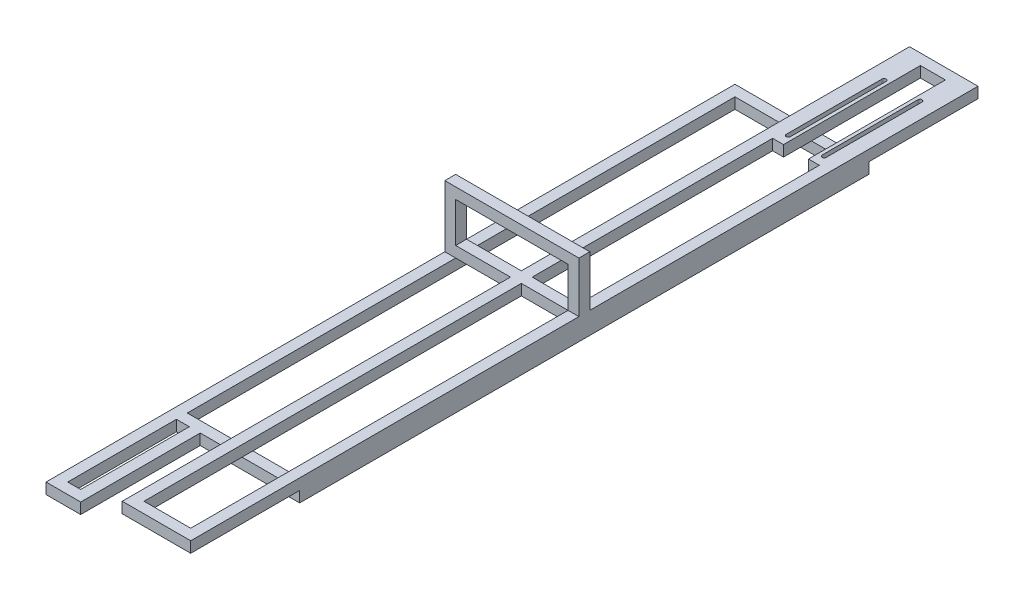
SolidWorks part; units mm, degrees
ref_plane "Front Plane" through (0, 0, 0) normal (0, 0, 1) x (1, 0, 0)
ref_plane "Top Plane" through (0, 0, 0) normal (0, 1, 0) x (1, 0, 0)
ref_plane "Right Plane" through (0, 0, 0) normal (1, 0, 0) x (0, 0, -1)
sketch "Sketch1" plane through (0, 0, 0) normal (0, 1, 0) x (1, 0, 0)
  line L1 (-50, 575) -> (50, 575)
  line L2 (-50, 575) -> (-50, -575)
  line L3 (-50, -575) -> (50, -575)
  line L4 (50, 575) -> (50, -575)
  line L8 (-34.125, 559.125) -> (34.125, 559.125)
  line L9 (34.125, 559.125) -> (34.125, -559.125)
  line L10 (-34.125, -559.125) -> (34.125, -559.125)
  line L11 (-34.125, 559.125) -> (-34.125, -559.125)
  point P4 (0, 575)
  point P6 (50, 0)
  dimension "D1" = 100
  dimension "D2" = 1150
  dimension "D3" = 15.875
extrude "Boss-Extrude1" add sketch "Sketch1" along normal blind 15.875
sketch "Sketch3" plane through (0, 15.875, 0) normal (0, 1, 0) x (1, 0, 0)
  line L0 (-145.875, 558.625) -> (-145.875, -591.375) construction
  line L2 (34.125, -223.912) -> (34.125, 400)
  line L3 (34.125, 400) -> (-130, 400)
  line L4 (-130, 220.5939) -> (-130, 400)
  line L6 (50, 415.875) -> (-145.875, 415.875)
  line L7 (-145.875, 217.7568) -> (-145.875, 415.875)
  line L9 (50, -312.7388) -> (50, 415.875)
  line L10 (-8.7312, 0) -> (8.7312, 0) construction
  line L11 (50, -312.7388) -> (50, -415.875)
  line L13 (-145.875, 217.7568) -> (-145.875, -415.875)
  line L14 (50, -415.875) -> (-145.875, -415.875)
  line L15 (-130, 220.5939) -> (-130, -400)
  line L16 (34.125, -223.912) -> (34.125, -400)
  line L18 (34.125, -400) -> (-130, -400)
  line L19 (50, -575) -> (50, 575) construction
  line L20 (50, -312.7388) -> (-145.875, 217.7568) construction
  line L21 (34.125, -223.912) -> (-130, 220.5939) construction
  point P0 (50, -312.7388)
  point P6 (-145.875, 415.875)
  point P12 (34.125, 0)
  point P22 (50, 0)
  dimension "D1" = 400
  dimension "D3" = 15.875
extrude "Boss-Extrude2" add sketch "Sketch3" against normal blind 15.875 from surface starting at face at (0, 0, 0)
sketch "Sketch5" plane through (0, 0, 0) normal (0, 0, 1) x (1, 0, 0)
  line L0 (-145.875, 959.91) -> (-145.875, -15.875) construction
  line L1 (50, 0) -> (-145.875, 0)
  line L2 (50, 0) -> (50, 90)
  line L3 (50, 90) -> (-145.875, 90)
  line L4 (-145.875, 0) -> (-145.875, 90)
  line L5 (34.125, 74.125) -> (-130, 74.125)
  line L6 (-130, 15.875) -> (-130, 74.125)
  line L7 (34.125, 15.875) -> (-130, 15.875)
  line L8 (34.125, 15.875) -> (34.125, 74.125)
  dimension "D1" = 90
  dimension "D2" = 15.875
extrude "Boss-Extrude3" add sketch "Sketch5" along normal mid plane 15.875
sketch "Sketch6" plane through (0, 0, 0) normal (0, -1, 0) x (1, 0, 0)
  line L6 (-34.125, -559.125) -> (-18.25, -559.125)
  line L7 (-34.125, -559.125) -> (-34.125, -359.125)
  line L8 (-34.125, -359.125) -> (-18.25, -359.125)
  line L9 (-18.25, -559.125) -> (-18.25, -359.125)
  line L10 (34.125, -559.125) -> (18.25, -559.125)
  line L11 (34.125, -559.125) -> (34.125, -359.125)
  line L12 (34.125, -359.125) -> (18.25, -359.125)
  line L13 (18.25, -559.125) -> (18.25, -359.125)
  line L14 (34.125, -559.125) -> (-34.125, -559.125) construction
  dimension "D1" = 15.875
  dimension "D2" = 15.875
  dimension "D4" = 200
extrude "Boss-Extrude4" add sketch "Sketch6" against normal blind 15.875
sketch "Sketch7" plane through (0, 0, 0) normal (0, -1, 0) x (1, 0, 0)
  line L0 (-26.1875, -374.125) -> (-26.1875, -514.125) construction
  line L1 (-23.1875, -374.125) -> (-23.1875, -514.125)
  line L2 (-29.1875, -374.125) -> (-29.1875, -514.125)
  line L3 (26.1875, -374.125) -> (26.1875, -514.125) construction
  line L4 (29.1875, -374.125) -> (29.1875, -514.125)
  line L5 (23.1875, -374.125) -> (23.1875, -514.125)
  line L6 (-18.25, -359.125) -> (-34.125, -359.125) construction
  line L7 (34.125, -359.125) -> (18.25, -359.125) construction
  arc A0 (-23.1875, -374.125) -> (-29.1875, -374.125) centre (-26.1875, -374.125) ccw
  arc A1 (-29.1875, -514.125) -> (-23.1875, -514.125) centre (-26.1875, -514.125) ccw
  arc A2 (29.1875, -374.125) -> (23.1875, -374.125) centre (26.1875, -374.125) ccw
  arc A3 (23.1875, -514.125) -> (29.1875, -514.125) centre (26.1875, -514.125) ccw
  point P2 (-26.1875, -444.125)
  point P7 (26.1875, -444.125)
  point P17 (-26.1875, -359.125)
  point P20 (26.1875, -359.125)
  dimension "D1" = 3
  dimension "D2" = 140
  dimension "D3" = 15
extrude "Cut-Extrude1" cut sketch "Sketch7" against normal blind 15.875
sketch "Sketch8" plane through (0, 0, 0) normal (0, 1, 0) x (1, 0, 0)
  line L1 (-95.25, -590.5) -> (-145.875, -590.5)
  line L2 (-95.25, -590.5) -> (-95.25, -400)
  line L3 (-95.25, -400) -> (-145.875, -400)
  line L4 (-145.875, -590.5) -> (-145.875, -400)
  line L5 (-130, -400) -> (-50, -400) construction
  line L6 (-111.125, -415.875) -> (-130, -415.875)
  line L7 (-130, -574.625) -> (-130, -415.875)
  line L8 (-111.125, -574.625) -> (-130, -574.625)
  line L9 (-111.125, -574.625) -> (-111.125, -415.875)
  line L10 (-145.875, -7.9375) -> (-145.875, -415.875) construction
  line L11 (-95.25, -590.5) -> (-111.125, -590.5) construction
  point P5 (-145.875, -400)
  point P7 (-97.9375, -400)
  dimension "D3" = 50.625
  dimension "D1" = 15.875
extrude "Boss-Extrude5" add sketch "Sketch8" against normal blind 15.875
